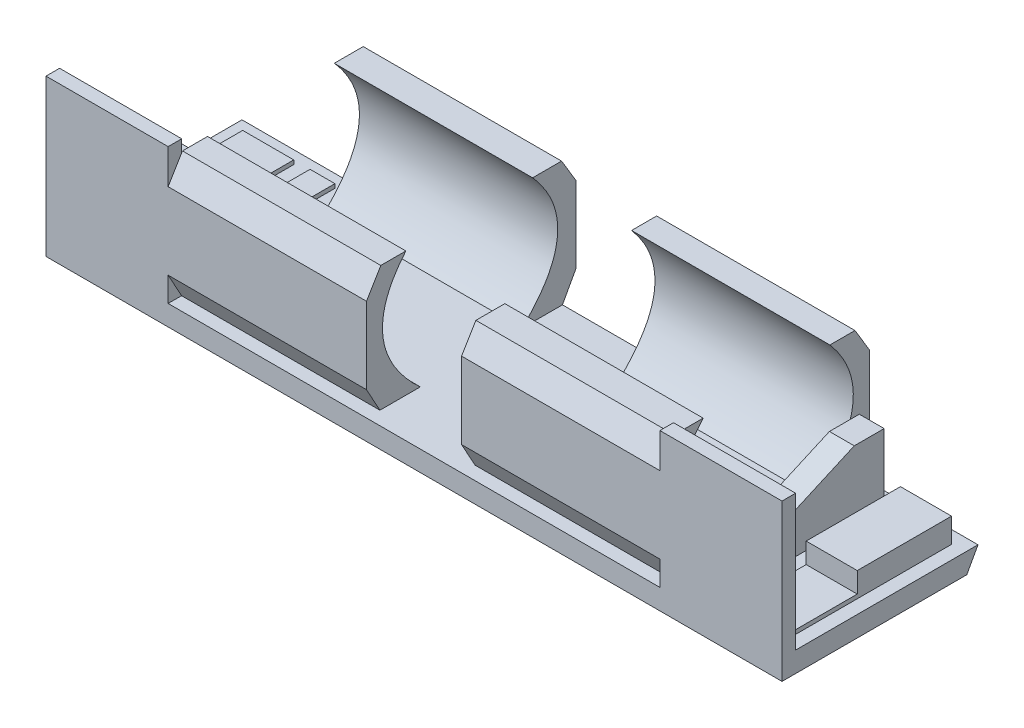
SolidWorks part; units mm, degrees
material "ABS"
ref_plane "前视基准面" through (0, 0, 0) normal (0, 0, 1) x (1, 0, 0)
ref_plane "上视基准面" through (0, 0, 0) normal (0, 1, 0) x (1, 0, 0)
ref_plane "右视基准面" through (0, 0, 0) normal (1, 0, 0) x (0, 0, -1)
sketch "草图1" plane through (0, 0, 0) normal (0, 1, 0) x (1, 0, 0)
  line L0 (-2.643, 5.97) -> (-1.843, 5.97) construction
  line L1 (-2.643, -5.97) -> (-6.803, -5.97) construction
  line L2 (-2.643, -5.97) -> (-2.643, 5.97) construction
  line L3 (-2.643, 5.97) -> (-6.803, 5.97) construction
  line L4 (-6.803, -5.97) -> (-6.803, 5.97) construction
  line L5 (-2.643, -5.97) -> (-6.803, 5.97) construction
  line L6 (-2.643, 5.97) -> (-6.803, -5.97) construction
  line L7 (-1.843, 5.97) -> (-1.843, -5.97) construction
  line L8 (-1.843, -5.97) -> (-2.643, -5.97) construction
  line L9 (-1.843, 5.97) -> (0.387, 5.97) construction
  line L10 (0.387, 5.97) -> (0.387, -5.97) construction
  line L11 (0.387, -5.97) -> (-1.843, -5.97) construction
  line L12 (0.387, 5.97) -> (1.187, 5.97) construction
  line L13 (1.187, 5.97) -> (1.187, -5.97) construction
  line L14 (1.187, -5.97) -> (0.387, -5.97) construction
  line L15 (1.187, 5.97) -> (16.187, 5.97) construction
  line L16 (16.187, 5.97) -> (16.187, -5.97) construction
  line L17 (16.187, -5.97) -> (1.187, -5.97) construction
  line L18 (1.387, 6.17) -> (1.387, 3.45)
  line L19 (16.187, -3.25) -> (1.187, -3.25) construction
  line L20 (16.187, -3.25) -> (16.187, 3.25) construction
  line L21 (16.187, 3.25) -> (1.187, 3.25) construction
  line L22 (1.187, -3.25) -> (1.187, 3.25) construction
  line L23 (16.187, -3.25) -> (1.187, 3.25) construction
  line L24 (16.187, 3.25) -> (1.187, -3.25) construction
  line L25 (-2.843, -5.77) -> (-6.603, -5.77)
  line L26 (-2.843, -5.77) -> (-2.843, 5.77)
  line L27 (-2.843, 5.77) -> (-6.603, 5.77)
  line L28 (-6.603, -5.77) -> (-6.603, 5.77)
  line L29 (-2.843, -5.77) -> (-6.603, 5.77) construction
  line L30 (-2.843, 5.77) -> (-6.603, -5.77) construction
  line L31 (-1.643, -5.77) -> (0.187, -5.77)
  line L32 (-1.643, -5.77) -> (-1.643, 5.77)
  line L33 (-1.643, 5.77) -> (0.187, 5.77)
  line L34 (0.187, -5.77) -> (0.187, 5.77)
  line L35 (-1.643, -5.77) -> (0.187, 5.77) construction
  line L36 (-1.643, 5.77) -> (0.187, -5.77) construction
  line L37 (1.387, 3.45) -> (15.987, 3.45)
  line L38 (15.987, 3.45) -> (15.987, 6.17)
  line L39 (15.987, 6.17) -> (1.387, 6.17)
  line L40 (-13.1732, 0) -> (23.9155, 0) construction
  line L41 (15.987, -3.45) -> (15.987, -6.17)
  line L42 (15.987, -6.17) -> (1.387, -6.17)
  line L43 (1.387, -6.17) -> (1.387, -3.45)
  line L44 (1.387, -3.45) -> (15.987, -3.45)
  line L45 (15.987, 3.45) -> (15.987, -3.45)
  line L46 (1.387, 3.45) -> (1.387, -3.45)
  line L47 (1.387, 6.17) -> (-7.603, 6.17)
  line L48 (-7.603, 6.17) -> (-7.603, -6.17)
  line L49 (-7.603, -6.17) -> (1.387, -6.17)
  point P0 (-4.723, 0)
  point P5 (8.687, 0)
  point P19 (-4.723, 0)
  point P24 (-0.728, 0)
  dimension "D1" = 4.16
  dimension "D2" = 11.94
  dimension "D3" = 0.8
  dimension "D4" = 2.23
  dimension "D5" = 0.8
  dimension "D6" = 15
  dimension "D7" = 15
  dimension "D8" = 6.5
  dimension "D9" = 0.2
  dimension "D10" = 0.2
  dimension "D11" = 0.2
  dimension "D12" = 0.2
  dimension "D13" = 0.2
  dimension "D14" = 0.2
  dimension "D15" = 0.2
  dimension "D16" = 0.2
  dimension "D17" = 0.2
  dimension "D18" = 0.2
  dimension "D19" = 0.8
extrude "凸台-拉伸1" add sketch "草图1" against normal blind 1 contours L48 L49 L43 L46 L18 L47 L25 L28 L27 L26 L34 L31 L32 L33 | L44 L43 L42 L41 | L37 L46 L44 L45 | L38 L39 L18 L37 | L28 L25 L26 L27 | L31 L34 L33 L32 region at (8.687, 0, -4.81) region at (-2.6812, 0, 0) region at (8.687, 0, 0) region at (8.687, 0, 4.81) region at (-4.723, 0, 0) region at (-0.728, 0, 0)
extrude "凸台-拉伸2" add sketch "草图1<3>" along normal blind 10 contours L28 L25 L26 L27 | L31 L34 L33 L32 | L44 L43 L42 L41 | L38 L39 L18 L37 region at (8.687, 0, -4.81) region at (8.687, 0, 4.81) region at (-4.723, 0, 0) region at (-0.728, 0, 0)
sketch "草图1<3>" plane through (0, 0, 0) normal (0, 1, 0) x (1, 0, 0) same geometry as "草图1"
sketch "草图4" plane through (15.987, 0, 0) normal (1, 0, 0) x (0, 0, -1)
  line L0 (6.17, 10) -> (7.7076, 7.4436)
  line L1 (7.7076, 7.4436) -> (7.7076, 1.8053)
  line L2 (7.7076, 1.8053) -> (6.17, -1)
  line L3 (0, 2.2205) -> (0, -2.201) construction
  line L4 (-7.7076, 1.8053) -> (-6.17, -1)
  line L5 (-6.17, 10) -> (-7.7076, 7.4436)
  line L6 (-7.7076, 7.4436) -> (-7.7076, 1.8053)
  line L7 (-6.17, 10) -> (-6.17, -1)
  line L8 (6.17, 10) -> (6.17, -1)
extrude "凸台-拉伸3" add sketch "草图4" against normal blind 14.6
sketch "草图3" plane through (15.987, 0, 0) normal (1, 0, 0) x (0, 0, -1)
  line L0 (3.45, 0) -> (3.7432, 0)
  line L1 (3.45, 10) -> (3.5974, 10.1362)
  line L2 (6.17, 0) -> (6.17, 10) construction
  line L4 (3.45, 10) -> (3.45, 0)
  line L6 (-3.45, 0) -> (-3.7432, 0)
  line L7 (-3.45, 10) -> (-3.7432, 10.2945)
  line L8 (-3.45, 10) -> (-3.45, 0)
  spline S0 degree 2 poles (3.45, 0) (8.89, 5) (3.45, 10) knots 0 0 0 1 1 1 construction
  spline S1 degree 1 poles (3.5853, -0.1473) (3.5853, 10.1473) knots 0 0 1 1 construction
  spline S2 degree 3 poles (3.5853, -0.1473) (3.8077, 0.0571) (4.2497, 0.4898) (4.9947, 1.3335) (5.7235, 2.4028) (6.2513, 3.6955) (6.4294, 5) (6.2513, 6.3045) (5.7235, 7.5972) (4.9947, 8.6665) (4.2497, 9.5102) (3.8077, 9.9429) (3.5853, 10.1473) knots 0 0 0 0 0.0625 0.125 0.25 0.375 0.5 0.625 0.75 0.875 0.9375 1 1 1 1 only from (3.7432, 0) to (3.5974, 10.1362)
  spline S3 degree 3 poles (-3.7432, 0) (-3.782, 0.0356) (-3.8495, 0.0983) (-4.072, 0.309) (-4.4617, 0.6983) (-5.1526, 1.4807) (-5.8814, 2.5501) (-6.4092, 3.8428) (-6.5872, 5.1473) (-6.4092, 6.4517) (-5.8814, 7.7444) (-5.1526, 8.8138) (-4.4617, 9.5962) (-4.072, 9.9855) (-3.8494, 10.1962) (-3.782, 10.2589) (-3.7432, 10.2945) knots 0 0 0 0 0.010893 0.018156 0.0625 0.125 0.25 0.375 0.5 0.625 0.75 0.875 0.9375 0.98185 0.98911 1 1 1 1
  point P0 (6.17, 5)
  dimension "D1" = 0.2
extrude "切除-拉伸1" cut sketch "草图3" against normal blind 14.6
sketch "草图5" plane through (0.187, 0, 0) normal (1, 0, 0) x (0, 0, -1)
  line L0 (5.77, 10) -> (5.77, 0) construction
  line L1 (1.17, 2.8) -> (-3.5697, 4.9019)
  line L2 (-3.5697, 4.9019) -> (-5.77, 4.9019)
  line L3 (-3.5697, 0.3) -> (1.17, 0.3) construction
  line L4 (1.17, 10.4322) -> (1.17, 0.3) construction
  line L5 (-5.77, 0) -> (5.77, 0) construction
  line L6 (5.77, 0.3) -> (1.17, 0.3)
  line L7 (1.17, 2.8) -> (1.17, 0.3)
  line L8 (-5.77, 10) -> (-5.77, 0) construction
  line L9 (-5.77, 4.9019) -> (-5.77, 10)
  line L10 (-5.77, 10) -> (5.77, 10)
  line L11 (3.7431, 10) -> (6.17, 10) construction
  line L12 (5.77, 10) -> (5.77, 0.3)
  dimension "D1" = 4.6
  dimension "D2" = 0.3
  dimension "D3" = 2.5
extrude "切除-拉伸2" cut sketch "草图5" against normal blind 14.6
sketch "草图6" plane through (-2.843, 0, 0) normal (1, 0, 0) x (0, 0, -1)
  line L0 (1.17, 5.5386) -> (1.17, 1.8)
  line L1 (1.17, 2.8) -> (1.17, 0.3) construction
  line L2 (1.17, 1.8) -> (-3.7955, 1.8)
  line L3 (-3.7955, 1.8) -> (-5.77, 1.8)
  line L4 (-5.77, 4.9019) -> (-5.77, 0) construction
  line L5 (-5.77, 1.8) -> (-5.77, 5.5386)
  line L6 (-5.77, 5.5386) -> (1.17, 5.5386)
  line L7 (1.17, 0.3) -> (5.77, 0.3) construction
  dimension "D1" = 1.5
extrude "切除-拉伸3" cut sketch "草图6" against normal blind 14.6
ref_plane "基准面1" through (19.487, 0, 0) normal (1, 0, 0) x (0, 0, -1)
ref_plane "基准面2" through (0, 0, -12.7076) normal (0, 0, -1) x (-1, 0, 0)
ref_axis "基准轴1" through (19.487, -1.5501, 0) along (0, 1, 0)
pattern_circular "阵列(圆周)1" count 2 every 180 about axis through (19.487, -1.5501, 0) along (0, 1, 0) of bodies 111
sketch "草图7" plane through (1.387, 0, 0) normal (-1, 0, 0) x (0, 0, 1)
  line L1 (-10.4365, 12.0579) -> (10.2118, 12.0579)
  line L2 (-10.4365, 12.0579) -> (-10.4365, 9.1973)
  line L3 (-10.4365, 9.1973) -> (10.2118, 9.1973)
  line L4 (10.2118, 12.0579) -> (10.2118, 9.1973)
extrude "切除-拉伸4" cut sketch "草图7" against normal blind 38.6
sketch "草图8" plane through (0, 0, 0) normal (0, 1, 0) x (1, 0, 0)
  line L0 (-7.603, 6.17) -> (-7.603, -6.17) construction
  line L1 (46.577, -9.5243) -> (-7.603, -9.5243)
  line L2 (46.577, -9.5243) -> (46.577, 9.5243)
  line L3 (46.577, 9.5243) -> (-7.603, 9.5243)
  line L4 (-7.603, -9.5243) -> (-7.603, 9.5243)
  line L5 (46.577, -9.5243) -> (-7.603, 9.5243) construction
  line L6 (46.577, 9.5243) -> (-7.603, -9.5243) construction
  line L8 (22.987, -14.0243) -> (15.987, -14.0243)
  line L9 (22.987, -14.0243) -> (22.987, -9.5243)
  line L10 (22.987, -9.5243) -> (15.987, -9.5243)
  line L11 (15.987, -14.0243) -> (15.987, -9.5243)
  line L12 (22.987, -14.0243) -> (15.987, -9.5243) construction
  line L13 (22.987, -9.5243) -> (15.987, -14.0243) construction
  line L14 (9.2293, 0) -> (27.9561, 0) construction
  circle A0 centre (19.487, -11.7743) radius 1.6
  point P0 (19.487, 0)
  point P8 (19.487, -11.7743)
  dimension "D1" = 7
  dimension "D3" = 3.2
  dimension "D2" = 4.5
extrude "凸台-拉伸4" add sketch "草图8" against normal blind 1.5 contours L4 L1 L2 L3 | L11 L8 L9 L1 A0 | L3 region at (19.487, 0, 0) region at (22.9038, 0, 11.7743)
sketch "草图9" plane through (0, 0, 0) normal (0, 1, 0) x (1, 0, 0)
  line L0 (46.577, -9.5243) -> (46.577, 9.5243) construction
  line L1 (-7.603, 9.5243) -> (46.577, 9.5243)
  line L2 (-7.603, 9.5243) -> (-7.603, 7.7243)
  line L3 (-7.603, 7.7243) -> (46.577, 7.7243)
  line L4 (46.577, 9.5243) -> (46.577, 7.7243)
  dimension "D1" = 1.8
extrude "凸台-拉伸5" add sketch "草图9" along normal blind 7
sketch "草图10" plane through (0, 0, -7.7243) normal (0, 0, 1) x (1, 0, 0)
  line L0 (-2.843, 0) -> (-6.603, 0) construction
  line L1 (-7.603, 7) -> (-7.603, 0) construction
  line L2 (41.817, 0) -> (45.577, 0) construction
  line L3 (46.577, 7) -> (46.577, 0) construction
  circle A0 centre (-4.603, 2.5) radius 1.65
  circle A1 centre (43.577, 2.5) radius 1.65
  point P4 (-7.603, 3.5)
  dimension "D1" = 2.5
  dimension "D3" = 2.5
  dimension "D2" = 3
  dimension "D4" = 3
extrude "切除-拉伸5" cut sketch "草图10" against normal blind 5
extrude "凸台-拉伸6" add sketch "草图8<3>" along normal blind 2 contours L11 L8 L9 L1 A0 | L3 region at (22.9038, 0, 11.7743)
sketch "草图8<3>" plane through (0, 0, 0) normal (0, 1, 0) x (1, 0, 0) same geometry as "草图8"
sketch "草图11" plane through (0, 0, 0) normal (0, 1, 0) x (1, 0, 0)
  line L0 (-7.603, 7.7243) -> (-7.603, -9.5243) construction
  line L1 (-7.603, -7.7076) -> (46.577, -7.7076)
  line L2 (-7.603, -7.7076) -> (-7.603, -14.361)
  line L3 (-7.603, -14.361) -> (46.577, -14.361)
  line L4 (46.577, -7.7076) -> (46.577, -14.361)
  line L5 (46.577, -9.5243) -> (46.577, 7.7243) construction
  line L6 (37.587, -7.7076) -> (22.987, -7.7076) construction
extrude "切除-拉伸6" cut sketch "草图11" against normal mid plane 10
sketch "草图12" plane through (46.577, 0, 0) normal (1, 0, 0) x (0, 0, -1)
  line L0 (7.7076, 1.8053) -> (5.896, -1.5)
  line L1 (-7.7076, -1.5) -> (9.5243, -1.5) construction
  line L2 (5.896, -1.5) -> (9.5243, -1.5)
  line L3 (9.5243, -1.5) -> (9.5243, 7.1462)
  line L4 (9.5243, 7.1462) -> (7.7243, 7)
  line L5 (7.7243, 7) -> (7.7076, 1.8053)
extrude "切除-拉伸7" cut sketch "草图12" against normal up to surface (54.18 mm away) up to face at (-7.603, 1.8333, -3.1803)
sketch "草图13" plane through (0, 0, 0) normal (0, 1, 0) x (1, 0, 0)
  line L0 (37.587, -7.7076) -> (37.587, -6.6528) construction
  line L1 (46.577, -7.7076) -> (37.587, -7.7076)
  line L2 (46.577, -7.7076) -> (46.577, -6.7076)
  line L3 (46.577, -6.7076) -> (37.587, -6.7076)
  line L4 (37.587, -7.7076) -> (37.587, -6.7076)
  line L6 (-7.603, -7.7076) -> (1.387, -7.7076)
  line L7 (-7.603, -7.7076) -> (-7.603, -6.7076)
  line L8 (-7.603, -6.7076) -> (1.387, -6.7076)
  line L9 (1.387, -7.7076) -> (1.387, -6.7076)
  dimension "D1" = 1
  dimension "D2" = 1
extrude "凸台-拉伸7" add sketch "草图13" along normal blind 10
